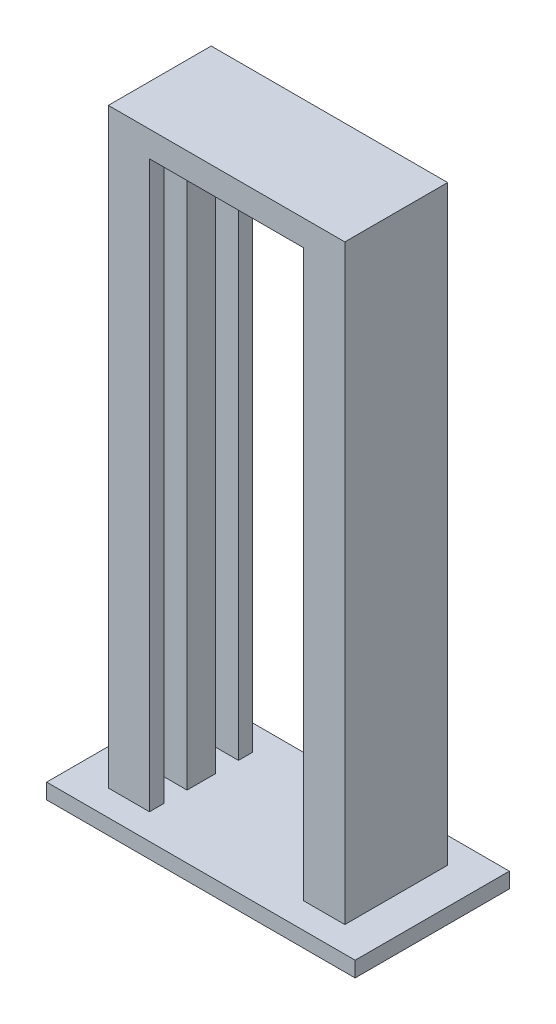
SolidWorks part; units mm, degrees
ref_plane "Front Plane" through (0, 0, 0) normal (0, 0, 1) x (1, 0, 0)
ref_plane "Top Plane" through (0, 0, 0) normal (0, 1, 0) x (1, 0, 0)
ref_plane "Right Plane" through (0, 0, 0) normal (1, 0, 0) x (0, 0, -1)
sketch "Sketch1" plane through (0, 0, 0) normal (0, 1, 0) x (1, 0, 0)
  line L1 (30, 15) -> (-30, 15)
  line L2 (30, 15) -> (30, -15)
  line L3 (30, -15) -> (-30, -15)
  line L4 (-30, 15) -> (-30, -15)
  line L5 (30, 15) -> (-30, -15) construction
  line L6 (30, -15) -> (-30, 15) construction
  point P0 (0, 0)
  dimension "D1" = 30
  dimension "D2" = 60
extrude "Boss-Extrude1" add sketch "Sketch1" along normal blind 3
sketch "Sketch2" plane through (0, 3, 0) normal (0, 1, 0) x (1, 0, 0)
  line L0 (0, 0) -> (-30, 0) construction
  line L1 (-30, 15) -> (-30, -15) construction
  line L2 (0, 0) -> (0, 15) construction
  line L3 (30, 15) -> (-30, 15) construction
  line L4 (15, -10) -> (23, -10)
  line L5 (-15, 10) -> (-23, 10)
  line L6 (-15, 10) -> (-15, -10)
  line L7 (-15, -10) -> (-23, -10)
  line L8 (-23, 10) -> (-23, -10)
  line L9 (-15, 10) -> (-23, -10) construction
  line L10 (-15, -10) -> (-23, 10) construction
  line L11 (23, 10) -> (23, -10)
  line L12 (15, 10) -> (23, 10)
  line L13 (15, 10) -> (15, -10)
  point P5 (-19, 0)
  dimension "D1" = 8
  dimension "D2" = 20
  dimension "D3" = 15
extrude "Boss-Extrude2" add sketch "Sketch2" along normal blind 110
sketch "Sketch3" plane through (0, 113, 0) normal (0, 1, 0) x (1, 0, 0)
  line L0 (-15, -10) -> (-15, 10) construction
  line L1 (-15, 7.3102) -> (-20.5, 7.3102)
  line L2 (-15, 7.3102) -> (-15, 2.8102)
  line L3 (-15, 2.8102) -> (-20.5, 2.8102)
  line L4 (-20.5, 7.3102) -> (-20.5, 2.8102)
  line L5 (-15, -10) -> (-15, 10) construction
  line L6 (-15, -2.6898) -> (-20.5, -2.6898)
  line L7 (-15, -2.6898) -> (-15, -7.1898)
  line L8 (-15, -7.1898) -> (-20.5, -7.1898)
  line L9 (-20.5, -2.6898) -> (-20.5, -7.1898)
  line L10 (0, 0) -> (0, 9.8393) construction
  line L11 (15, -7.1898) -> (20.5, -7.1898)
  line L12 (20.5, -2.6898) -> (20.5, -7.1898)
  line L13 (15, -2.6898) -> (20.5, -2.6898)
  line L14 (15, -2.6898) -> (15, -7.1898)
  line L15 (15, 2.8102) -> (20.5, 2.8102)
  line L16 (20.5, 7.3102) -> (20.5, 2.8102)
  line L17 (15, 7.3102) -> (20.5, 7.3102)
  line L18 (15, 7.3102) -> (15, 2.8102)
  dimension "D1" = 5.5
  dimension "D2" = 5.5
  dimension "D3" = 4.5
  dimension "D4" = 4.5
  dimension "D5" = 5.5
extrude "Cut-Extrude1" cut sketch "Sketch3" against normal blind 110
sketch "Sketch4" plane through (0, 113, 0) normal (0, 1, 0) x (1, 0, 0)
  line L1 (-23, 10) -> (23, 10)
  line L2 (-23, 10) -> (-23, -10)
  line L3 (-23, -10) -> (23, -10)
  line L4 (23, 10) -> (23, -10)
extrude "Boss-Extrude3" add sketch "Sketch4" along normal blind 5
